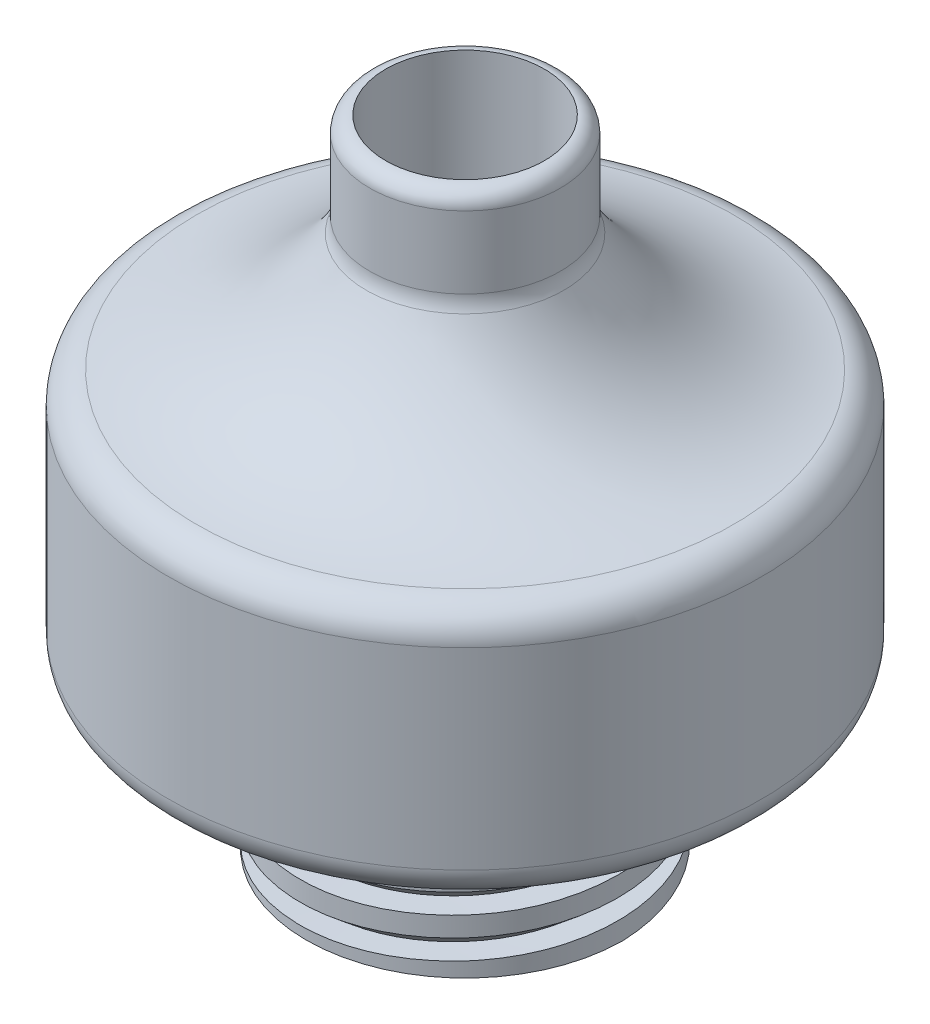
SolidWorks part; units mm, degrees
ref_plane "Ön Düzlem" through (0, 0, 0) normal (0, 0, 1) x (1, 0, 0)
ref_plane "Üst Düzlem" through (0, 0, 0) normal (0, 1, 0) x (1, 0, 0)
ref_plane "Sağ Düzlem" through (0, 0, 0) normal (1, 0, 0) x (0, 0, -1)
sketch "Çizim1" plane through (0, 0, 0) normal (0, 0, 1) x (1, 0, 0)
  line L0 (0, -1.0279) -> (5, -1.0279)
  line L1 (5, -1.0279) -> (5, 3.9721)
  line L2 (5, 3.9721) -> (8.3246, 3.9721)
  line L3 (9.3246, 4.9721) -> (9.3246, 11.0349)
  line L5 (0, 15.9721) -> (0, -1.0279)
  line L6 (3, 16.2064) -> (3, 18.4721)
  line L7 (2.5, 18.9721) -> (0, 18.9721)
  line L8 (0, 18.9721) -> (0, 15.9721)
  arc A0 (8.4496, 12.027) -> (3.1126, 15.7455) centre (9.3246, 18.9721) cw
  arc A1 (3, 16.2064) -> (3.1126, 15.7455) centre (4, 16.2064) ccw
  arc A2 (8.3246, 3.9721) -> (9.3246, 4.9721) centre (8.3246, 4.9721) ccw
  arc A3 (9.3246, 11.0349) -> (8.4496, 12.027) centre (8.3246, 11.0349) ccw
  arc A4 (3, 18.4721) -> (2.5, 18.9721) centre (2.5, 18.4721) ccw
  point P12 (3, 15.9721)
  point P15 (9.3246, 3.9721)
  point P18 (9.3246, 11.9721)
  point P21 (3, 18.9721)
  dimension "D5" = 7
  dimension "D7" = 1
  dimension "D8" = 1
  dimension "D9" = 0.5
  dimension "D1" = 5
  dimension "D2" = 3
  dimension "D4" = 5
  dimension "D6" = 20
revolve "Döndür1" add sketch "Çizim1" angle 360 about L5
sketch "Çizim2" plane through (0, 18.9721, 0) normal (0, 1, 0) x (1, 0, 0)
  circle A0 centre (0, 0) radius 2.5
extrude "Kes-Ekstrüzyon1" cut sketch "Çizim2" against normal up to next
sketch "Çizim5" plane through (0, -1.0279, 0) normal (0, -1, 0) x (1, 0, 0)
  circle A0 centre (0, 0) radius 5
curve "Helis/Spiral1" pitch 1.25 height 5 turns 4
sketch "Çizim7" plane through (0, 0, 0) normal (0, 0, 1) x (1, 0, 0)
  line L0 (-4.2508, -1.0279) -> (-5.0854, -0.3296)
  line L1 (-5, -1.0279) -> (5, -1.0279) construction
  line L2 (-5.0854, -0.3296) -> (-5.0854, -1.0279)
  line L3 (-5.0854, -1.0279) -> (-4.2508, -1.0279)
sweep "Kes-Süpür1" cut profiles "Çizim7" path "Helis/Spiral1"
